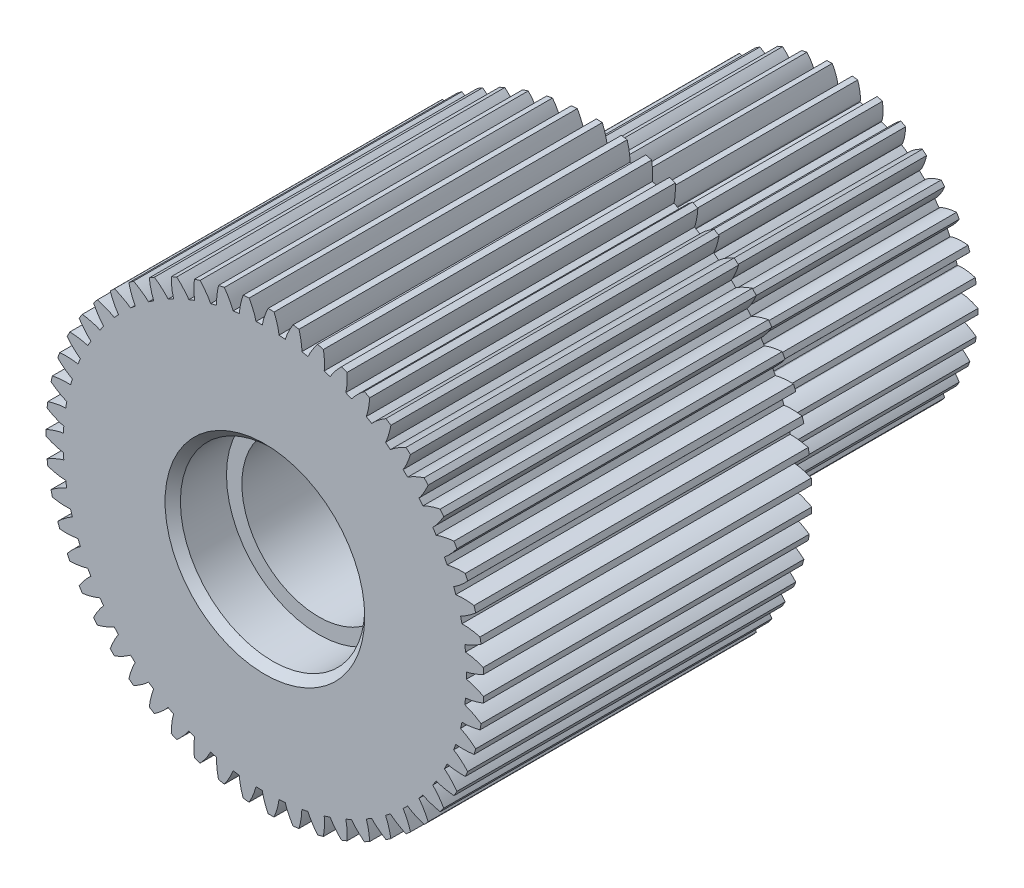
SolidWorks part; units mm, degrees
material "PLA"
ref_plane "Front Plane" through (0, 0, 0) normal (0, 0, 1) x (1, 0, 0)
ref_plane "Top Plane" through (0, 0, 0) normal (0, 1, 0) x (1, 0, 0)
ref_plane "Right Plane" through (0, 0, 0) normal (1, 0, 0) x (0, 0, -1)
sketch "Sketch1" plane through (0, 0, 0) normal (0, 0, 1) x (1, 0, 0)
  circle A0 centre (0, 0) radius 14.25
  dimension "D1" = 28.5
extrude "Boss-Extrude1" add sketch "Sketch1" along normal mid plane 21.3651
sketch "Sketch2" plane through (0, 0, 0) normal (0, 0, 1) x (1, 0, 0)
  line L0 (0, 0) -> (13.7487, 0.1878) construction
  line L1 (0, 0) -> (13.75, 0) construction
  line L2 (0, 0) -> (13.7487, -0.1878) construction
  line L3 (12.9171, -0.1764) -> (13.1238, -0.1792)
  line L4 (12.9196, 0.1764) -> (13.1238, 0.1792)
  circle A0 centre (0, 0) radius 13.75 construction
  circle A1 centre (0, 0) radius 12.9208 construction
  circle A2 centre (0, 0) radius 13.125
  circle A3 centre (0, 0) radius 14.25 construction
  circle A4 centre (0, 0) radius 14.25
  spline S0 degree 4 poles (12.9196, 0.1764) (12.924, 0.1766) (12.9364, 0.1771) (12.9597, 0.1789) (12.9978, 0.183) (13.0462, 0.1897) (13.1086, 0.2003) (13.1818, 0.2152) (13.262, 0.2341) (13.3488, 0.2572) (13.4351, 0.2827) (13.5207, 0.3103) (13.6056, 0.3398) (13.708, 0.3778) (13.8301, 0.4265) (13.9716, 0.4882) (14.1308, 0.5636) (14.2914, 0.6462) (14.448, 0.7322) (14.6046, 0.8246) (14.7548, 0.9177) (14.909, 1.0199) (15.0503, 1.117) (15.2064, 1.2318) (15.3317, 1.3261) (15.4945, 1.4568) (15.5899, 1.5359) (15.7006, 1.6305) (15.7492, 1.6737) (15.7792, 1.7002) knots 0 0 0 0 0 0.005377 0.015084 0.028532 0.04661 0.064855 0.092111 0.119476 0.146842 0.174209 0.201575 0.228941 0.256307 0.307035 0.361767 0.4165 0.471232 0.525964 0.580697 0.635429 0.690161 0.744894 0.799626 0.854358 0.909091 0.954545 1 1 1 1 1 construction
  spline S1 degree 4 poles (12.9196, 0.1764) (12.924, 0.1766) (12.9364, 0.1771) (12.9597, 0.1789) (12.9978, 0.183) (13.0462, 0.1897) (13.1086, 0.2003) (13.1818, 0.2152) (13.262, 0.2341) (13.3488, 0.2572) (13.4351, 0.2827) (13.5207, 0.3103) (13.6056, 0.3398) (13.708, 0.3778) (13.8301, 0.4265) (13.9716, 0.4882) (14.1308, 0.5636) (14.2914, 0.6462) (14.448, 0.7322) (14.6046, 0.8246) (14.7548, 0.9177) (14.909, 1.0199) (15.0503, 1.117) (15.2064, 1.2318) (15.3317, 1.3261) (15.4592, 1.4285) (15.521, 1.479) (15.5524, 1.5052) knots 0 0 0 0 0 0.005377 0.015084 0.028532 0.04661 0.064855 0.092111 0.119476 0.146842 0.174209 0.201575 0.228941 0.256307 0.307035 0.361767 0.4165 0.471232 0.525964 0.580697 0.635429 0.690161 0.744894 0.799626 0.854358 0.909091 0.909091 0.909091 0.909091 0.909091
  spline S2 degree 4 poles (12.9171, -0.1764) (12.9215, -0.1765) (12.9339, -0.1771) (12.9573, -0.1789) (12.9954, -0.1829) (13.0438, -0.1897) (13.1062, -0.2003) (13.1794, -0.2152) (13.2595, -0.234) (13.3464, -0.2572) (13.4326, -0.2827) (13.5182, -0.3103) (13.6031, -0.3397) (13.7055, -0.3777) (13.8276, -0.4265) (13.9692, -0.4882) (14.1283, -0.5635) (14.2889, -0.6462) (14.4456, -0.7322) (14.6021, -0.8245) (14.7524, -0.9177) (14.9065, -1.0199) (15.0479, -1.117) (15.204, -1.2317) (15.3293, -1.3261) (15.492, -1.4568) (15.5874, -1.5358) (15.6981, -1.6305) (15.7468, -1.6737) (15.7768, -1.7002) knots 0 0 0 0 0 0.005377 0.015084 0.028532 0.04661 0.064855 0.092111 0.119476 0.146842 0.174209 0.201575 0.228941 0.256307 0.307035 0.361767 0.4165 0.471232 0.525964 0.580697 0.635429 0.690161 0.744894 0.799626 0.854358 0.909091 0.954545 1 1 1 1 1 construction
  spline S3 degree 4 poles (12.9171, -0.1764) (12.9215, -0.1765) (12.9339, -0.1771) (12.9573, -0.1789) (12.9954, -0.1829) (13.0438, -0.1897) (13.1062, -0.2003) (13.1794, -0.2152) (13.2595, -0.234) (13.3464, -0.2572) (13.4326, -0.2827) (13.5182, -0.3103) (13.6031, -0.3397) (13.7055, -0.3777) (13.8276, -0.4265) (13.9692, -0.4882) (14.1283, -0.5635) (14.2889, -0.6462) (14.4456, -0.7322) (14.6021, -0.8245) (14.7524, -0.9177) (14.9065, -1.0199) (15.0479, -1.117) (15.204, -1.2317) (15.3293, -1.3261) (15.4568, -1.4284) (15.5185, -1.479) (15.5499, -1.5051) knots 0 0 0 0 0 0.005377 0.015084 0.028532 0.04661 0.064855 0.092111 0.119476 0.146842 0.174209 0.201575 0.228941 0.256307 0.307035 0.361767 0.4165 0.471232 0.525964 0.580697 0.635429 0.690161 0.744894 0.799626 0.854358 0.909091 0.909091 0.909091 0.909091 0.909091
  dimension "D1" = 27.5
  dimension "D2" = 25.8415
  dimension "D3" = 26.25
  dimension "D4" = 0.782
  dimension "D5" = 0.782
extrude "Cut-Extrude1" cut sketch "Sketch2" against normal through all both and the other way through all contours A2 A4 region at (13.7878, -0.0005, 0)
pattern_circular "CirPattern2" count 55 over 360 about axis through (0, 0, 10.6826) along (0, 0, -1) of "Cut-Extrude1"
sketch "Sketch3" plane through (0, 0, 10.6826) normal (0, 0, 1) x (1, 0, 0)
  circle A0 centre (0, 0) radius 5
  dimension "D1" = 10
sketch "Sketch4" plane through (0, 0, -10.6826) normal (0, 0, -1) x (-1, 0, 0)
  circle A0 centre (0, 0) radius 9.25
  dimension "D1" = 18.5
extrude "Boss-Extrude2" add sketch "Sketch4" along normal blind 15.8109
sketch "Sketch5" plane through (0, 0, -26.4934) normal (0, 0, -1) x (-1, 0, 0)
  line L0 (0, 0) -> (9.25, 0) construction
  line L1 (0, 0) -> (9.2458, 0.2772) construction
  line L2 (0, 0) -> (9.2458, -0.2772) construction
  line L3 (8.1981, 0.2458) -> (8.1213, 0.2435)
  line L4 (8.1981, -0.2458) -> (8.1213, -0.2435)
  circle A0 centre (0, 0) radius 8.2223 construction
  circle A1 centre (0, 0) radius 8.125
  arc A2 (9.2269, -0.6536) -> (9.2269, 0.6536) centre (0, 0) ccw
  spline S0 degree 4 poles (8.1981, 0.2458) (8.2009, 0.2459) (8.2088, 0.2464) (8.2237, 0.2478) (8.2479, 0.2508) (8.2927, 0.2578) (8.3462, 0.2687) (8.4062, 0.2834) (8.4704, 0.3017) (8.525, 0.3188) (8.5792, 0.3372) (8.633, 0.3569) (8.6977, 0.3821) (8.7749, 0.4144) (8.8643, 0.4551) (8.9648, 0.5047) (9.0661, 0.559) (9.1649, 0.6153) (9.2636, 0.6757) (9.3582, 0.7365) (9.4552, 0.8032) (9.5441, 0.8664) (9.6423, 0.941) (9.721, 1.0024) (9.8232, 1.0872) (9.8831, 1.1385) (9.9525, 1.1999) (9.983, 1.2279) (10.0018, 1.2451) knots 0 0 0 0 0 0.005377 0.015084 0.028532 0.04661 0.092111 0.119476 0.146842 0.174209 0.201575 0.228941 0.256307 0.307035 0.361767 0.4165 0.471232 0.525964 0.580697 0.635429 0.690161 0.744894 0.799626 0.854358 0.909091 0.954545 1 1 1 1 1 construction
  spline S1 degree 4 poles (8.1981, 0.2458) (8.2009, 0.2459) (8.2088, 0.2464) (8.2237, 0.2478) (8.2479, 0.2508) (8.2927, 0.2578) (8.3462, 0.2687) (8.4062, 0.2834) (8.4704, 0.3017) (8.525, 0.3188) (8.5792, 0.3372) (8.633, 0.3569) (8.6977, 0.3821) (8.7749, 0.4144) (8.8643, 0.4551) (8.9648, 0.5047) (9.0661, 0.559) (9.1649, 0.6153) (9.2636, 0.6757) (9.3582, 0.7365) (9.4552, 0.8032) (9.5441, 0.8664) (9.6423, 0.941) (9.721, 1.0024) (9.8011, 1.0688) (9.8398, 1.1016) (9.8596, 1.1186) knots 0 0 0 0 0 0.005377 0.015084 0.028532 0.04661 0.092111 0.119476 0.146842 0.174209 0.201575 0.228941 0.256307 0.307035 0.361767 0.4165 0.471232 0.525964 0.580697 0.635429 0.690161 0.744894 0.799626 0.854358 0.909091 0.909091 0.909091 0.909091 0.909091
  spline S2 degree 4 poles (8.1981, -0.2458) (8.2009, -0.2459) (8.2088, -0.2464) (8.2237, -0.2478) (8.2479, -0.2508) (8.2927, -0.2578) (8.3462, -0.2687) (8.4062, -0.2834) (8.4704, -0.3017) (8.525, -0.3188) (8.5792, -0.3372) (8.633, -0.3569) (8.6977, -0.3821) (8.7749, -0.4144) (8.8643, -0.4551) (8.9648, -0.5047) (9.0661, -0.559) (9.1649, -0.6153) (9.2636, -0.6757) (9.3582, -0.7365) (9.4552, -0.8032) (9.5441, -0.8664) (9.6423, -0.941) (9.721, -1.0024) (9.8232, -1.0872) (9.8831, -1.1385) (9.9525, -1.1999) (9.983, -1.2279) (10.0018, -1.2451) knots 0 0 0 0 0 0.005377 0.015084 0.028532 0.04661 0.092111 0.119476 0.146842 0.174209 0.201575 0.228941 0.256307 0.307035 0.361767 0.4165 0.471232 0.525964 0.580697 0.635429 0.690161 0.744894 0.799626 0.854358 0.909091 0.954545 1 1 1 1 1 construction
  spline S3 degree 4 poles (8.1981, -0.2458) (8.2009, -0.2459) (8.2088, -0.2464) (8.2237, -0.2478) (8.2479, -0.2508) (8.2927, -0.2578) (8.3462, -0.2687) (8.4062, -0.2834) (8.4704, -0.3017) (8.525, -0.3188) (8.5792, -0.3372) (8.633, -0.3569) (8.6977, -0.3821) (8.7749, -0.4144) (8.8643, -0.4551) (8.9648, -0.5047) (9.0661, -0.559) (9.1649, -0.6153) (9.2636, -0.6757) (9.3582, -0.7365) (9.4552, -0.8032) (9.5441, -0.8664) (9.6423, -0.941) (9.721, -1.0024) (9.8011, -1.0688) (9.8398, -1.1016) (9.8596, -1.1186) knots 0 0 0 0 0 0.005377 0.015084 0.028532 0.04661 0.092111 0.119476 0.146842 0.174209 0.201575 0.228941 0.256307 0.307035 0.361767 0.4165 0.471232 0.525964 0.580697 0.635429 0.690161 0.744894 0.799626 0.854358 0.909091 0.909091 0.909091 0.909091 0.909091
  dimension "D2" = 16.25
  dimension "D3" = 18.5
  dimension "D1" = 16.4446
  dimension "D4" = 1.717
  dimension "D5" = 1.717
extrude "Cut-Extrude2" cut sketch "Sketch5" against normal up to surface (15.8109 mm away) contours A2 A1 region at (-8.7837, 0, -26.4934) up to face at (9.25, 0, -10.6826)
pattern_circular "CirPattern3" count 35 over 360 about axis through (0, 0, -26.4934) along (0, 0, 1) of "Cut-Extrude2"
extrude "Cut-Extrude3" cut sketch "Sketch3" against normal through all contours A0
sketch "Sketch7" plane through (0, 0, -26.4934) normal (0, 0, -1) x (-1, 0, 0)
  circle A0 centre (0, 0) radius 6
  dimension "D1" = 12
extrude "Cut-Extrude4" cut sketch "Sketch7" against normal blind 3.5
ref_plane "Plane1" through (0, 0, -7.9054) normal (0, 0, -1) x (-1, 0, 0)
mirror "Mirror1" about plane through (0, 0, -7.9054) normal (0, 0, -1) of "Cut-Extrude4"
chamfer "Chamfer1" distance 0.5 angle 45 2 edges at (-6, 0, 10.6826) (-6, 0, -26.4934)
equation "\"module\" = 0.5"
equation "\"pressure angle\" = 20.0"
equation "\"h_a\" = 0.5"
equation "\"h_b\" = 0.625"
equation "\"clr_tip_root\" = 0.125"
equation "\"D1@Sketch1\" = \"dp_p_b\" + 2 * \"h_a\""
equation "\"D1@Boss-Extrude1\" = \"fw_p_b\""
equation "\"D1@Sketch2\" = \"dp_p_b\""
equation "\"D2@Sketch2\"= \"db_p_b\""
equation "\"D3@Sketch2\" = \"dp_p_b\" - 2 * \"h_b\""
equation "\"Nr_s\" = 170"
equation "\"pressure_angle\" = 20.0"
equation "\"h_f\" = 0.625"
equation "\"dp_r_s\" = 85.0"
equation "\"bearing_ID\" = 75"
equation "\"bearing_OD\" = 95"
equation "\"bearing_height\" = 10"
equation "\"clearance_planet\" = 1.5"
equation "\"case_dist\" = 6.5"
equation "\"Motor_case_OD_max\" = 131.3"
equation "\"case_mounting_PCD\" = 123.8"
equation "\"bearing mount thickness\" = 8"
equation "\"case_mounting_hole_dia\" = 3"
equation "\"output_mounting_PCD\" = 103"
equation "\"output_mounting_hole_dia\" = 4"
equation "\"clearance_case_mount_holes_shell_thickness\" = 1"
equation "\"motor_case_OD_base\" = 121.8"
equation "\"sec_carrier_thickness\" = 5"
equation "\"sun_coupler_hub_thickness\" = 4"
equation "\"clearance_sun_coupler_sec_carrier\" = 1.5"
equation "\"clearance_motor_and_case\" = 5"
equation "\"motor_OD\" = 106.8"
equation "\"Motor_case_thickness\" = 2.5"
equation "\"Motor_case_ID\" = 116.8"
equation "\"case_mounting_hole_shift\" = 1.0"
equation "\"output_mounting_nut_wrench_size\" = 7"
equation "\"output_mounting_nut_thickness\" = 3.2"
equation "\"case_mounting_hole_allen_socket_dia\" = 5.5"
equation "\"output_mounting_nut_depth\" = 3"
equation "\"case_mounting_bolt_depth\" = 4.5"
equation "\"Ns\" = 80"
equation "\"ring_radial_thickness\" = 5"
equation "\"ring_to_chamfer_clearance\" = 1.5"
equation "\"Motor_case_OD_base_to_chamfer\" = 5"
equation "\"pattern_offset_from_motor_case_OD_base\" = 3"
equation "\"pattern_bulge_dia\" = 3"
equation "\"pattern_num_bulge\" = 18"
equation "\"pattern_depth\" = 2"
equation "\"motor_height\" = 47.6"
equation "\"case_mounting_wrench_size\" = 5.5"
equation "\"case_mounting_nut_clearance\" = 2"
equation "\"base_plate_thickness\" = 4"
equation "\"case_mounting_nut_thickness\" = 2.4"
equation "\"case_mounting_surface_height\" = 4"
equation "\"motor_mount_hole_PCD\" = 40"
equation "\"motor_mount_hole_dia\" = 5"
equation "\"motor_mount_hole_num\" = 4"
equation "\"central_hole_offset_from_motor_mount_PCD\" = 5"
equation "\"wire_slot_dist_from_center\" = 45.5"
equation "\"wire_slot_length\" = 10"
equation "\"wire_slot_radius\" = 3"
equation "\"driver_upper_holes_dist_from_center\" = 29"
equation "\"driver_lower_holes_dist_from_center\" = 13"
equation "\"driver_side_holes_dist_from_center\" = 22.5"
equation "\"driver_mount_holes_dia\" = 3"
equation "\"driver_mount_inserts_OD\" = 4.8"
equation "\"driver_mount_thickness\" = 1.5"
equation "\"driver_mount_height\" = 6"
equation "\"air_flow_hole_offset\" = 3"
equation "\"num_planet\" = 5"
equation "\"planet_pin_bolt_dia\" = 5"
equation "\"planet_pin_socket_head_dia\" = 8.5"
equation "\"carrier_PCD\" = 67.5"
equation "\"planet_shaft_dia\" = 8"
equation "\"planet_shaft_step_offset\" = 1"
equation "\"carrier_trapezoidal_support_sun_offset\" = 5"
equation "\"carrier_trapezoidal_support_hole_PCD_offset_bearing_ID\" = 4"
equation "\"carrier_trapezoidal_support_hole_dia\" = 3"
equation "\"carrier_trapezoidal_support_hole_socket_head_dia\" = 5.5"
equation "\"carrier_bearing_step_width\" = 1.5"
equation "\"standard_clearance_1_5mm\" = 1.5"
equation "\"standard_fillet_1_5mm\" = 1.5"
equation "\"sun_shaft_bearing_OD\" = 16"
equation "\"sun_shaft_bearing_width\" = 5"
equation "\"standard_bearing_insertion_chamfer\" = 0.5"
equation "\"carrier_trapezoidal_support_hole_wrench_size\" = 5.5"
equation "\"planet_pin_bolt_wrench_size\" = 8"
equation "\"planet_bearing_OD\" = 12"
equation "\"planet_bearing_width\" = 3.5"
equation "\"planet_bore\" = 10"
equation "\"D1@Sketch3\"=\"planet_bore\""
equation "\"Np_b\" = 55"
equation "\"dp_s\" = 40.0"
equation "\"db_s\" = 37.58770483143634"
equation "\"fw_s_calc\" = 4.872946430626146"
equation "\"alpha_s\" = 0.8539582918412272"
equation "\"beta_s\" = 0.5420834163175456"
equation "\"dp_p_b\" = 27.5"
equation "\"db_p_b\" = 25.84154707161248"
equation "\"fw_p_s\" = 15.81085678360617"
equation "\"alpha_p_b\" = 0.8539582918412449"
equation "\"beta_p_b\" = 1.564810689044783"
equation "\"motor_output_hole_PCD\" = 23"
equation "\"motor_output_hole_dia\" = 4"
equation "\"motor_output_hole_num\" = 4"
equation "\"sun_shaft_bearing_ID\" = 8"
equation "\"sun_hub_dia\" = 30.0"
equation "\"sun_central_bolt_dia\" = 5"
equation "\"sun_central_bolt_socket_head_dia\" = 8.5"
equation "\"fw_s_used\" = 44.67596466627659"
equation "\"motor_output_hole_CSK_OD\" = 8"
equation "\"motor_output_hole_CSK_head_height\" = 2.0"
equation "\"bearing_retainer_thickness\" = 2"
equation "\"Np_s\" = 35"
equation "\"fw_p_b\" = 21.365107882670422"
equation "\"dp_p_s\" = 17.5"
equation "\"db_p_s\" = 16.444620863753396"
equation "\"alpha_p_s\" = 0.8539582918412556"
equation "\"beta_p_s\" = 3.434940559174632"
equation "\"D1@Sketch4\"=\"dp_p_s\" + 2 * \"h_a\""
equation "\"D1@Boss-Extrude2\"=\"fw_p_s\""
equation "\"D2@Sketch5\"=\"dp_p_s\" - 2 * \"h_b\""
equation "\"D3@Sketch5\"=\"dp_p_s\"+2 * \"h_a\" "
equation "\"D1@Sketch5\"=\"db_p_s\""
equation "\"D1@CirPattern3\"=\"Np_s\""
equation "\"D4@Sketch5\"=\"beta_p_s\"/2"
equation "\"D5@Sketch5\"=\"beta_p_s\"/2"
equation "\"D4@Sketch2\"=\"beta_p_b\"/2"
equation "\"D5@Sketch2\"=\"beta_p_b\"/2"
equation "\"D1@Sketch7\"=\"planet_bearing_OD\""
equation "\"D1@Cut-Extrude4\"=\"planet_bearing_width\""
equation "\"D1@Chamfer1\"=\"standard_bearing_insertion_chamfer\""
equation "\"D1@CirPattern2\"=\"Np_b\""
equation "\"Nr_b\" = 190"
equation "\"dp_r_b\" = 95.0"
equation "\"db_r_b\" = 89.2707989746613"
equation "\"fw_r_b\" = 21.365107882670422"
equation "\"alpha_r_b\" = 0.8539582918412414"
equation "\"beta_r_b\" = 2.655285004735114"
equation "\"ring_OD_b\" = 105.0"
equation "\"Fillet10\"= IIF ( \"ring_OD_b\" > ( \"bearing_OD\" + 2 * \"bearing mount thickness\" ) , \"suppressed\" , \"unsuppressed\" )"
equation "\"Fillet11\"= IIF ( \"ring_OD_b\" < ( \"bearing_OD\" + 2 * \"bearing mount thickness\" ) , \"suppressed\" , \"unsuppressed\" )"
equation "\"clr_tip_root_s\" = 0.125"
equation "\"db_r_s\" = 79.87387276680222"
equation "\"fw_r_s\" = 14.31085678360617"
equation "\"alpha_r_s\" = 0.8539582918412307"
equation "\"beta_r_s\" = 2.766740113094226"
equation "\"small_ring_case_thickness\" = 4"
equation "\"carrier_thickness\" = 4"
equation "\"small_ring_output_wall_thickness\" = 5"
equation "\"small_ring_output_wall_to_bearing_shaft_attachement_hole_dia\" = 4"
equation "\"small_ring_output_wall_to_bearing_shaft_attachement_hole_depth\" = 6.5"
equation "\"small_ring_output_wall_to_bearing_shaft_attachement_nut_wrench\" = 7"
equation "\"small_ring_output_wall_to_bearing_shaft_attachement_nut_thickness\" = 3.2"
equation "\"small_ring_output_wall_to_bearing_shaft_attachement_hole_pcd\" = 12"
equation "\"small_ring_output_wall_to_bearing_shaft_attachement_hole_num\" = 3"
equation "\"small_ring_output_wall_to_bearing_shaft_attachement_hole_CSK_OD\" = 8"
equation "\"small_ring_output_wall_to_bearing_shaft_attachement_hole_CSK_head_height\" = 2.0"
equation "\"carrier_small_ring_inner_bearing_ID\" = 20"
equation "\"carrier_small_ring_inner_bearing_OD\" = 32"
equation "\"carrier_small_ring_inner_bearing_height\" = 7"
equation "\"carrier_small_ring_inner_bearing_flap\" = 2"
equation "\"gear_casing_big_ring_to_bearing_dist\" = 24.81085678360617"
equation "\"gear_casing_thickness\" = 4"
